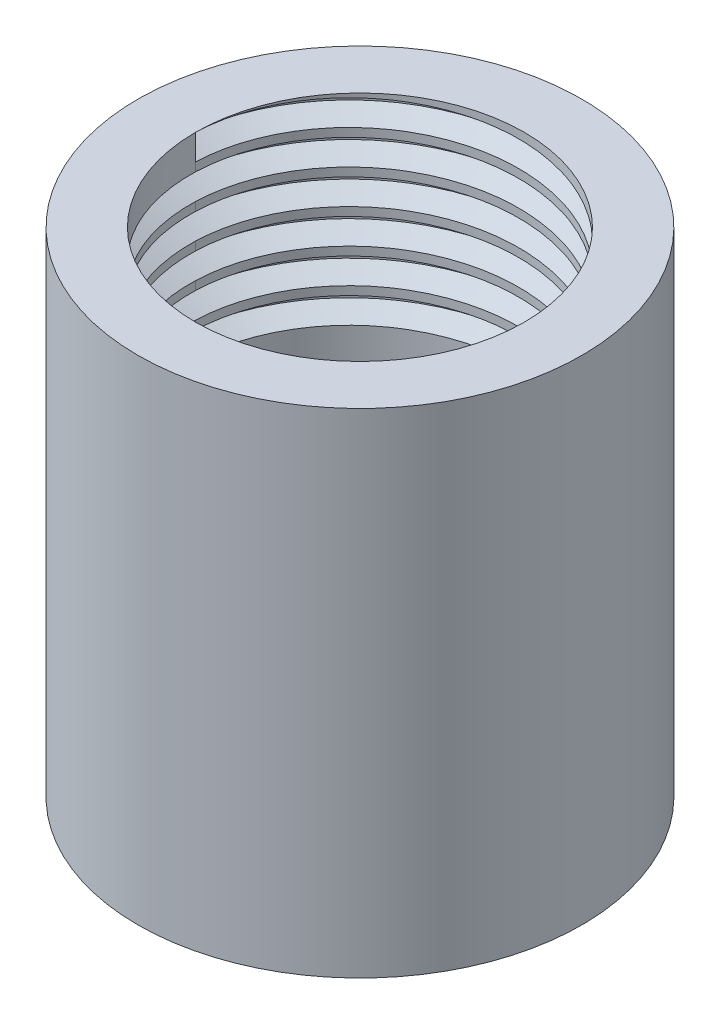
SolidWorks part; units mm, degrees
ref_plane "Front Plane" through (0, 0, 0) normal (0, 0, 1) x (1, 0, 0)
ref_plane "Top Plane" through (0, 0, 0) normal (0, 1, 0) x (1, 0, 0)
ref_plane "Right Plane" through (0, 0, 0) normal (1, 0, 0) x (0, 0, -1)
sketch "Sketch1" plane through (0, 0, 0) normal (0, 1, 0) x (1, 0, 0)
  circle A0 centre (0, 0) radius 13.716
  circle A1 centre (0, 0) radius 10.16
  circle A2 centre (0, 0) radius 2.54
  circle A3 centre (6.35, 0) radius 2.54
extrude "Boss-Extrude3" add sketch "Sketch1" along normal blind 5.08 contours A1 A3 A2 | A0 A1 region at (-13.3281, 0, 0) region at (-9.8726, 0, 0)
extrude "Boss-Extrude4" add sketch "Sketch1<9>" along normal blind 30.48 contours A0 A1 region at (-13.3281, 0, 0)
sketch "Sketch1<9>" plane through (0, 0, 0) normal (0, 1, 0) x (1, 0, 0) same geometry as "Sketch1"
thread "Thread1" pitch 2.1167 method cut profile "Thread Profile2" start angle 0, offset 0, length 12.7, pitch 2.1167, diameter 20.32
ref_plane "Plane2" through (-10.16, 30.48, 0) normal (0, 0, 1) x (-1, 0, 0)
sketch "Thread Profile2" plane through (-10.16, 30.48, 0) normal (0, 0, 1) x (-1, 0, 0)
  line L0 (0, 0) -> (0, 2.1167) construction
  line L1 (0, 0) -> (1.1457, 0.6615)
  line L2 (1.1457, 0.6615) -> (1.1457, 0.926)
  line L3 (1.1457, 0.926) -> (0, 1.5875)
  line L4 (1.1457, 0.7937) -> (0, 0.7937) construction
  line L11 (0, 0) -> (0, 1.5875)
  point P2 (0, 0)
  dimension "Pitch" = 2.1167
  dimension "Profile_Angle" = 60
  dimension "Profile_Land" = 0.2646
  dimension "Profile_Height" = 1.1457
sketch "Sketch15" plane through (0, 5.08, 0) normal (0, 1, 0) x (1, 0, 0)
  circle A0 centre (0, 0) radius 2.54
extrude "Boss-Extrude5" add sketch "Sketch15" against normal through all
hole_wizard "1/4-20 Tapped Hole1" positions "Sketch16" profile "Sketch17" tap size "1/4-20" standard "ANSI Inch" end condition through all
sketch "Sketch16" plane through (0, 5.08, 0) normal (0, 1, 0) x (1, 0, 0)
  point P0 (0, 0)
sketch "Sketch17" plane through (0, 5.08, 0) normal (1, 0, 0) x (0, 0, 1)
  line L0 (0, 0) -> (0, 5.08)
  line L1 (0, 5.08) -> (2.5527, 5.08)
  line L2 (2.5527, 5.08) -> (2.5527, 0)
  line L5 (2.5527, 0) -> (0, 0)
  line L11 (0, -6.35) -> (0, 107.95) construction
  dimension "Thru Tap Drill Dia." = 5.1054
  dimension "Thru Tap Drill Depth" = 5.08
cosmetic thread "Hole Thread1" parameters "D2"=6.35
